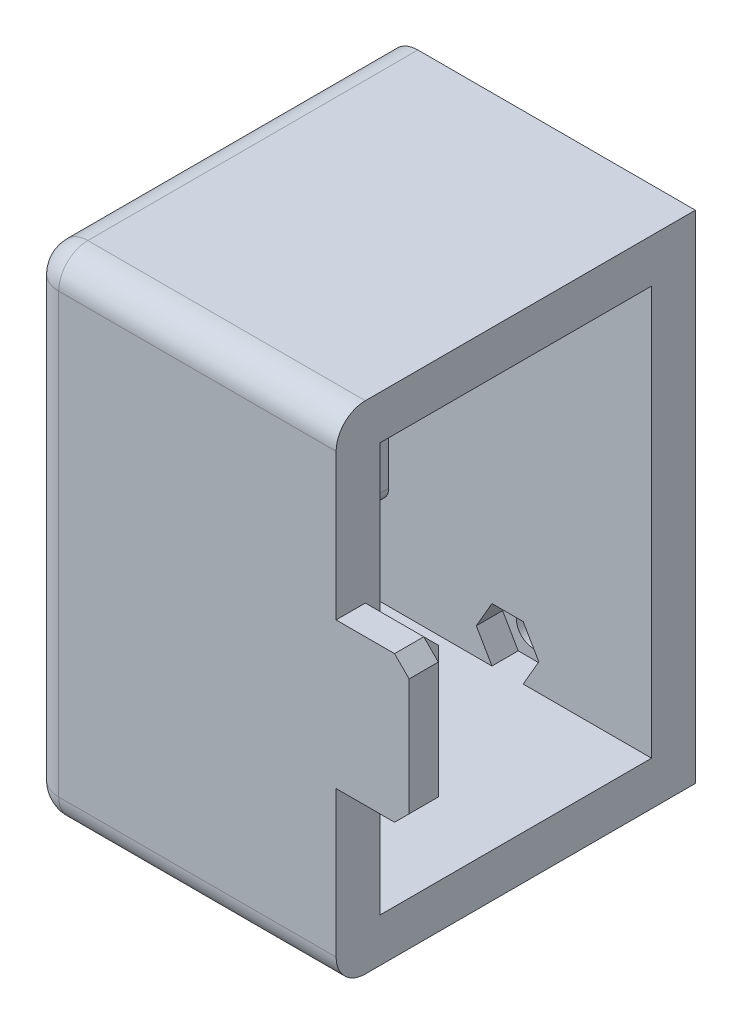
SolidWorks part; units mm, degrees
ref_plane "Front Plane" through (0, 0, 0) normal (0, 0, 1) x (1, 0, 0)
ref_plane "Top Plane" through (0, 0, 0) normal (0, 1, 0) x (1, 0, 0)
ref_plane "Right Plane" through (0, 0, 0) normal (1, 0, 0) x (0, 0, -1)
sketch "Sketch1" plane through (0, 0, 0) normal (0, 1, 0) x (1, 0, 0)
  line L0 (-16.51, 0) -> (16.51, 0)
  line L1 (16.51, 0) -> (16.51, 3.81)
  line L2 (16.51, 3.81) -> (-12.7, 3.81)
  line L3 (-12.7, 3.81) -> (-12.7, 27.432)
  line L4 (-12.7, 27.432) -> (10.16, 27.432)
  line L5 (10.16, 27.432) -> (10.16, 31.242)
  line L6 (10.16, 31.242) -> (-16.51, 31.242)
  line L7 (-16.51, 31.242) -> (-16.51, 0)
  line L8 (10.16, 3.81) -> (10.16, 0)
  point P9 (0, 0)
  dimension "D1" = 31.242
  dimension "D2" = 3.81
  dimension "D3" = 3.81
  dimension "D4" = 22.86
  dimension "D5" = 3.81
  dimension "D6" = 33.02
  dimension "D7" = 6.35
extrude "Boss-Extrude1" add sketch "Sketch1" along normal blind 21.59 and the other way blind 21.59 contours L8 L2 L3 L4 L5 L6 L7 L0 region at (-16.0992, 0, -15.621)
extrude "Boss-Extrude2" add sketch "Sketch1<4>" along normal blind 6.35 and the other way blind 6.35 contours L2 L8 L0 L1 region at (13.335, 0, -1.905)
sketch "Sketch1<4>" plane through (0, 0, 0) normal (0, 1, 0) x (1, 0, 0) same geometry as "Sketch1"
sketch "Sketch3" plane through (0, 21.59, 0) normal (0, 1, 0) x (1, 0, 0)
  line L0 (-16.51, 31.242) -> (-16.51, 0) construction
  line L1 (-16.51, 31.242) -> (10.16, 31.242)
  line L2 (-16.51, 31.242) -> (-16.51, 0)
  line L3 (-16.51, 0) -> (10.16, 0)
  line L4 (10.16, 31.242) -> (10.16, 0)
extrude "Boss-Extrude3" add sketch "Sketch3" against normal blind 3.81
mirror "Mirror1" about plane through (0, 0, 0) normal (0, 1, 0) of "Boss-Extrude3"
sketch "Sketch4" plane through (0, 0, -27.432) normal (0, 0, 1) x (1, 0, 0)
  line L0 (-16.51, 21.59) -> (10.16, 21.59) construction
  line L1 (0.3556, 15.4263) -> (-1.0033, 17.78)
  line L2 (-1.0033, 17.78) -> (-3.7211, 17.78)
  line L3 (-3.7211, 17.78) -> (-5.08, 15.4263)
  line L4 (-5.08, 15.4263) -> (-3.7211, 13.0726)
  line L5 (-3.7211, 13.0726) -> (-1.0033, 13.0726)
  line L6 (-1.0033, 13.0726) -> (0.3556, 15.4263)
  line L7 (-16.51, -21.59) -> (-16.51, 21.59) construction
  circle A0 centre (-2.3622, 15.4263) radius 2.3537 construction
  circle A1 centre (-2.3622, 15.4263) radius 1.524
  dimension "D4" = 3.048
  dimension "D1" = 5.4356
  dimension "D2" = 3.81
  dimension "D3" = 11.43
extrude "Cut-Extrude1" cut sketch "Sketch4" against normal blind 2.286
extrude "Cut-Extrude3" cut sketch "Sketch4<4>" against normal through all contours A1 region at (-2.3622, 15.4263, -27.432)
sketch "Sketch4<4>" plane through (0, 0, -27.432) normal (0, 0, 1) x (1, 0, 0) same geometry as "Sketch4"
mirror "Mirror2" about plane through (0, 0, 0) normal (0, 1, 0) of "Cut-Extrude1", "Cut-Extrude3"
sketch "Sketch6" plane through (-12.7, 0, 0) normal (1, 0, 0) x (0, 0, -1)
  line L1 (27.432, -17.78) -> (19.812, -17.78)
  line L2 (27.432, -17.78) -> (27.432, -10.16)
  line L3 (27.432, -10.16) -> (19.812, -10.16)
  line L4 (19.812, -17.78) -> (19.812, -10.16)
  dimension "D1" = 7.62
extrude "Cut-Extrude4" cut sketch "Sketch6" against normal through all
fillet "Fillet1" radius 2.54 5 edges at (-3.175, -21.59, 0) (-16.51, -21.59, -15.621) (-16.51, 0, 0) (-3.175, 21.59, 0) (-16.51, 21.59, -15.621)
fillet "Fillet2" radius 1.27 6 edges at (-12.7, -13.97, -19.812) (-12.7, -10.16, -23.622) (-16.51, -17.78, -23.622) (-16.51, -13.97, -19.812) (-16.51, -13.97, -27.432) (-16.51, -10.16, -23.622)
chamfer "Chamfer1" distance 1.27 angle 45 5 edges at (16.51, -6.35, -1.905) (13.335, -6.35, -3.81) (16.51, 0, -3.81) (13.335, 6.35, -3.81) (16.51, 6.35, -1.905)
chamfer "Chamfer2" distance 0.254 angle 45 2 edges at (-0.8382, -15.4263, -31.242) (-0.8382, 15.4263, -31.242)
